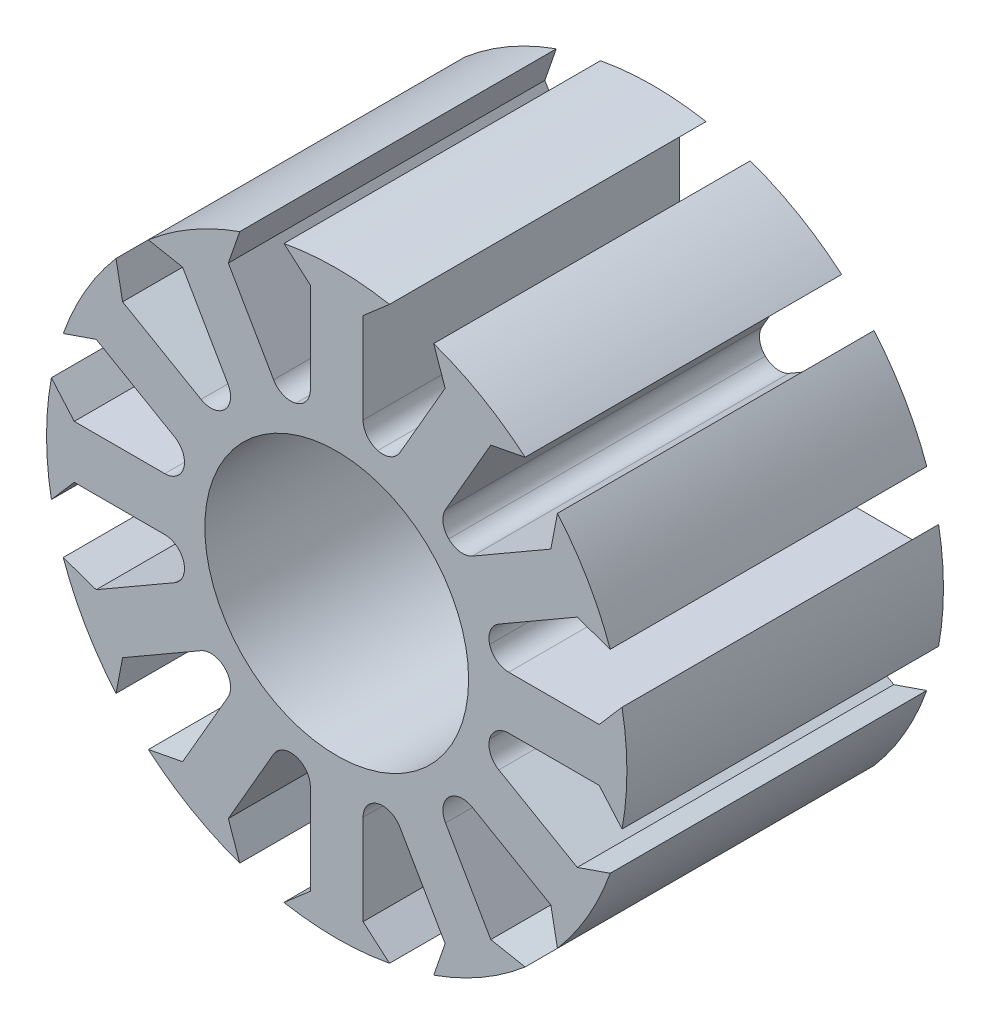
SolidWorks part; units mm, degrees
material "A286 Iron Base Superalloy"
ref_plane "Front Plane" through (0, 0, 0) normal (0, 0, 1) x (1, 0, 0)
ref_plane "Top Plane" through (0, 0, 0) normal (0, 1, 0) x (1, 0, 0)
ref_plane "Right Plane" through (0, 0, 0) normal (1, 0, 0) x (0, 0, -1)
sketch "Sketch1" plane through (0, 0, 0) normal (0, 0, 1) x (1, 0, 0)
  line L0 (-1, 9.9499) -> (-2, 10.8167)
  line L5 (1.5835, 4.7426) -> (4.1089, 9.1168)
  line L6 (3.3155, 3.7426) -> (5.841, 8.1168)
  line L11 (4.1089, 9.1168) -> (3.6763, 10.3675)
  line L12 (1, 4.899) -> (1, 9.9499)
  line L13 (1, 9.9499) -> (2, 10.8167)
  line L14 (5.841, 8.1168) -> (7.1404, 8.3675)
  line L16 (3.7426, 3.3155) -> (8.1168, 5.841)
  line L17 (-1, 4.899) -> (-1, 9.9499)
  line L18 (4.7426, 1.5835) -> (9.1168, 4.1089)
  line L19 (8.1168, 5.841) -> (8.3675, 7.1404)
  line L21 (9.1168, 4.1089) -> (10.3675, 3.6763)
  line L22 (4.899, 1) -> (9.9499, 1)
  line L23 (4.899, -1) -> (9.9499, -1)
  line L24 (9.9499, 1) -> (10.8167, 2)
  line L25 (9.9499, -1) -> (10.8167, -2)
  line L26 (4.7426, -1.5835) -> (9.1168, -4.1089)
  line L27 (3.7426, -3.3155) -> (8.1168, -5.841)
  line L28 (9.1168, -4.1089) -> (10.3675, -3.6763)
  line L29 (8.1168, -5.841) -> (8.3675, -7.1404)
  line L30 (3.3155, -3.7426) -> (5.841, -8.1168)
  line L31 (1.5835, -4.7426) -> (4.1089, -9.1168)
  line L32 (5.841, -8.1168) -> (7.1404, -8.3675)
  line L33 (4.1089, -9.1168) -> (3.6763, -10.3675)
  line L34 (1, -4.899) -> (1, -9.9499)
  line L35 (-1, -4.899) -> (-1, -9.9499)
  line L36 (1, -9.9499) -> (2, -10.8167)
  line L37 (-1, -9.9499) -> (-2, -10.8167)
  line L38 (-1.5835, -4.7426) -> (-4.1089, -9.1168)
  line L39 (-3.3155, -3.7426) -> (-5.841, -8.1168)
  line L40 (-4.1089, -9.1168) -> (-3.6763, -10.3675)
  line L41 (-5.841, -8.1168) -> (-7.1404, -8.3675)
  line L42 (-3.7426, -3.3155) -> (-8.1168, -5.841)
  line L43 (-4.7426, -1.5835) -> (-9.1168, -4.1089)
  line L44 (-8.1168, -5.841) -> (-8.3675, -7.1404)
  line L45 (-9.1168, -4.1089) -> (-10.3675, -3.6763)
  line L46 (-4.899, -1) -> (-9.9499, -1)
  line L47 (-4.899, 1) -> (-9.9499, 1)
  line L48 (-9.9499, -1) -> (-10.8167, -2)
  line L49 (-9.9499, 1) -> (-10.8167, 2)
  line L50 (-4.7426, 1.5835) -> (-9.1168, 4.1089)
  line L51 (-3.7426, 3.3155) -> (-8.1168, 5.841)
  line L52 (-9.1168, 4.1089) -> (-10.3675, 3.6763)
  line L53 (-8.1168, 5.841) -> (-8.3675, 7.1404)
  line L54 (-3.3155, 3.7426) -> (-5.841, 8.1168)
  line L55 (-1.5835, 4.7426) -> (-4.1089, 9.1168)
  line L56 (-5.841, 8.1168) -> (-7.1404, 8.3675)
  line L57 (-4.1089, 9.1168) -> (-3.6763, 10.3675)
  arc A0 (2, 10.8167) -> (-2, 10.8167) centre (0, 0) ccw
  arc A1 (-1, 4.899) -> (-1.5835, 4.7426) centre (0, 0) ccw
  arc A5 (-1, 4.899) -> (-1.5835, 4.7426) centre (0, 0) ccw
  arc A6 (7.1404, 8.3675) -> (3.6763, 10.3675) centre (0, 0) ccw
  arc A7 (3.7426, 3.3155) -> (3.3155, 3.7426) centre (0, 0) ccw
  arc A8 (10.3675, 3.6763) -> (8.3675, 7.1404) centre (0, 0) ccw
  arc A9 (4.899, 1) -> (4.7426, 1.5835) centre (0, 0) ccw
  arc A10 (10.8167, -2) -> (10.8167, 2) centre (0, 0) ccw
  arc A11 (4.7426, -1.5835) -> (4.899, -1) centre (0, 0) ccw
  arc A12 (8.3675, -7.1404) -> (10.3675, -3.6763) centre (0, 0) ccw
  arc A13 (3.3155, -3.7426) -> (3.7426, -3.3155) centre (0, 0) ccw
  arc A14 (3.6763, -10.3675) -> (7.1404, -8.3675) centre (0, 0) ccw
  arc A15 (1, -4.899) -> (1.5835, -4.7426) centre (0, 0) ccw
  arc A16 (-2, -10.8167) -> (2, -10.8167) centre (0, 0) ccw
  arc A17 (-1.5835, -4.7426) -> (-1, -4.899) centre (0, 0) ccw
  arc A18 (-7.1404, -8.3675) -> (-3.6763, -10.3675) centre (0, 0) ccw
  arc A19 (-3.7426, -3.3155) -> (-3.3155, -3.7426) centre (0, 0) ccw
  arc A20 (-10.3675, -3.6763) -> (-8.3675, -7.1404) centre (0, 0) ccw
  arc A21 (-4.899, -1) -> (-4.7426, -1.5835) centre (0, 0) ccw
  arc A22 (-10.8167, 2) -> (-10.8167, -2) centre (0, 0) ccw
  arc A23 (-4.7426, 1.5835) -> (-4.899, 1) centre (0, 0) ccw
  arc A24 (-8.3675, 7.1404) -> (-10.3675, 3.6763) centre (0, 0) ccw
  arc A25 (-3.3155, 3.7426) -> (-3.7426, 3.3155) centre (0, 0) ccw
  arc A26 (-3.6763, 10.3675) -> (-7.1404, 8.3675) centre (0, 0) ccw
  arc A27 (-1, 4.899) -> (-1.5835, 4.7426) centre (0, 0) ccw
  arc A28 (-1, 4.899) -> (-1.5835, 4.7426) centre (0, 0) ccw
  arc A29 (-1, 4.899) -> (-1.5835, 4.7426) centre (0, 0) ccw
  arc A30 (-1, 4.899) -> (-1.5835, 4.7426) centre (0, 0) ccw
  arc A31 (-1, 4.899) -> (-1.5835, 4.7426) centre (0, 0) ccw
  arc A32 (-1, 4.899) -> (-1.5835, 4.7426) centre (0, 0) ccw
  arc A33 (-1, 4.899) -> (-1.5835, 4.7426) centre (0, 0) ccw
  arc A34 (-1, 4.899) -> (-1.5835, 4.7426) centre (0, 0) ccw
  arc A35 (-1, 4.899) -> (-1.5835, 4.7426) centre (0, 0) ccw
  arc A36 (-1, 4.899) -> (-1.5835, 4.7426) centre (0, 0) ccw
  arc A37 (-3.3155, 3.7426) -> (-3.7426, 3.3155) centre (0, 0) ccw
  arc A38 (-3.3155, 3.7426) -> (-3.7426, 3.3155) centre (0, 0) ccw
  arc A39 (-3.3155, 3.7426) -> (-3.7426, 3.3155) centre (0, 0) ccw
  arc A40 (-3.3155, 3.7426) -> (-3.7426, 3.3155) centre (0, 0) ccw
  arc A41 (-3.3155, 3.7426) -> (-3.7426, 3.3155) centre (0, 0) ccw
  arc A42 (-3.3155, 3.7426) -> (-3.7426, 3.3155) centre (0, 0) ccw
  arc A43 (-3.3155, 3.7426) -> (-3.7426, 3.3155) centre (0, 0) ccw
  arc A44 (-3.3155, 3.7426) -> (-3.7426, 3.3155) centre (0, 0) ccw
  arc A45 (-3.3155, 3.7426) -> (-3.7426, 3.3155) centre (0, 0) ccw
  arc A46 (-3.3155, 3.7426) -> (-3.7426, 3.3155) centre (0, 0) ccw
  arc A47 (-3.3155, 3.7426) -> (-3.7426, 3.3155) centre (0, 0) ccw
  arc A48 (1.5835, 4.7426) -> (1, 4.899) centre (0, 0) ccw
  arc A49 (3.7426, 3.3155) -> (3.3155, 3.7426) centre (0, 0) ccw
  arc A50 (3.7426, 3.3155) -> (3.3155, 3.7426) centre (0, 0) ccw
  arc A51 (3.7426, 3.3155) -> (3.3155, 3.7426) centre (0, 0) ccw
  arc A52 (3.7426, 3.3155) -> (3.3155, 3.7426) centre (0, 0) ccw
  arc A53 (3.7426, 3.3155) -> (3.3155, 3.7426) centre (0, 0) ccw
  arc A54 (3.7426, 3.3155) -> (3.3155, 3.7426) centre (0, 0) ccw
  arc A55 (3.7426, 3.3155) -> (3.3155, 3.7426) centre (0, 0) ccw
  arc A56 (3.7426, 3.3155) -> (3.3155, 3.7426) centre (0, 0) ccw
  arc A57 (3.7426, 3.3155) -> (3.3155, 3.7426) centre (0, 0) ccw
  arc A58 (3.7426, 3.3155) -> (3.3155, 3.7426) centre (0, 0) ccw
  arc A59 (3.7426, 3.3155) -> (3.3155, 3.7426) centre (0, 0) ccw
  arc A60 (-4.7426, 1.5835) -> (-4.899, 1) centre (0, 0) ccw
  arc A61 (-4.7426, 1.5835) -> (-4.899, 1) centre (0, 0) ccw
  arc A62 (-4.7426, 1.5835) -> (-4.899, 1) centre (0, 0) ccw
  arc A63 (-4.7426, 1.5835) -> (-4.899, 1) centre (0, 0) ccw
  arc A64 (-4.7426, 1.5835) -> (-4.899, 1) centre (0, 0) ccw
  arc A65 (4.7426, -1.5835) -> (4.899, -1) centre (0, 0) ccw
  arc A66 (4.7426, -1.5835) -> (4.899, -1) centre (0, 0) ccw
  arc A67 (4.7426, -1.5835) -> (4.899, -1) centre (0, 0) ccw
  arc A68 (4.7426, -1.5835) -> (4.899, -1) centre (0, 0) ccw
  arc A69 (4.7426, -1.5835) -> (4.899, -1) centre (0, 0) ccw
  arc A70 (4.7426, -1.5835) -> (4.899, -1) centre (0, 0) ccw
  arc A71 (4.7426, -1.5835) -> (4.899, -1) centre (0, 0) ccw
  arc A72 (4.7426, -1.5835) -> (4.899, -1) centre (0, 0) ccw
  arc A73 (4.7426, -1.5835) -> (4.899, -1) centre (0, 0) ccw
  arc A74 (4.7426, -1.5835) -> (4.899, -1) centre (0, 0) ccw
  arc A75 (4.7426, -1.5835) -> (4.899, -1) centre (0, 0) ccw
  arc A76 (3.3155, -3.7426) -> (3.7426, -3.3155) centre (0, 0) ccw
  arc A77 (3.3155, -3.7426) -> (3.7426, -3.3155) centre (0, 0) ccw
  arc A78 (3.3155, -3.7426) -> (3.7426, -3.3155) centre (0, 0) ccw
  arc A79 (3.3155, -3.7426) -> (3.7426, -3.3155) centre (0, 0) ccw
  arc A80 (3.3155, -3.7426) -> (3.7426, -3.3155) centre (0, 0) ccw
  arc A81 (3.3155, -3.7426) -> (3.7426, -3.3155) centre (0, 0) ccw
  arc A82 (3.3155, -3.7426) -> (3.7426, -3.3155) centre (0, 0) ccw
  arc A83 (3.3155, -3.7426) -> (3.7426, -3.3155) centre (0, 0) ccw
  arc A84 (3.3155, -3.7426) -> (3.7426, -3.3155) centre (0, 0) ccw
  arc A85 (3.3155, -3.7426) -> (3.7426, -3.3155) centre (0, 0) ccw
  arc A86 (3.3155, -3.7426) -> (3.7426, -3.3155) centre (0, 0) ccw
  arc A87 (1, -4.899) -> (1.5835, -4.7426) centre (0, 0) ccw
  arc A88 (1, -4.899) -> (1.5835, -4.7426) centre (0, 0) ccw
  arc A89 (1, -4.899) -> (1.5835, -4.7426) centre (0, 0) ccw
  arc A90 (1, -4.899) -> (1.5835, -4.7426) centre (0, 0) ccw
  arc A91 (1, -4.899) -> (1.5835, -4.7426) centre (0, 0) ccw
  arc A92 (1, -4.899) -> (1.5835, -4.7426) centre (0, 0) ccw
  arc A93 (1, -4.899) -> (1.5835, -4.7426) centre (0, 0) ccw
  arc A94 (1, -4.899) -> (1.5835, -4.7426) centre (0, 0) ccw
  arc A95 (1, -4.899) -> (1.5835, -4.7426) centre (0, 0) ccw
  arc A96 (1, -4.899) -> (1.5835, -4.7426) centre (0, 0) ccw
  arc A97 (1, -4.899) -> (1.5835, -4.7426) centre (0, 0) ccw
  arc A98 (-1.5835, -4.7426) -> (-1, -4.899) centre (0, 0) ccw
  arc A99 (-1.5835, -4.7426) -> (-1, -4.899) centre (0, 0) ccw
  arc A100 (-1.5835, -4.7426) -> (-1, -4.899) centre (0, 0) ccw
  arc A101 (-1.5835, -4.7426) -> (-1, -4.899) centre (0, 0) ccw
  arc A102 (-1.5835, -4.7426) -> (-1, -4.899) centre (0, 0) ccw
  arc A103 (-1.5835, -4.7426) -> (-1, -4.899) centre (0, 0) ccw
  arc A104 (-1.5835, -4.7426) -> (-1, -4.899) centre (0, 0) ccw
  arc A105 (-1.5835, -4.7426) -> (-1, -4.899) centre (0, 0) ccw
  arc A106 (-1.5835, -4.7426) -> (-1, -4.899) centre (0, 0) ccw
  arc A107 (-1.5835, -4.7426) -> (-1, -4.899) centre (0, 0) ccw
  arc A108 (-1.5835, -4.7426) -> (-1, -4.899) centre (0, 0) ccw
  arc A109 (-4.7426, 1.5835) -> (-4.899, 1) centre (0, 0) ccw
  arc A110 (-4.7426, 1.5835) -> (-4.899, 1) centre (0, 0) ccw
  arc A111 (-4.7426, 1.5835) -> (-4.899, 1) centre (0, 0) ccw
  arc A112 (-4.7426, 1.5835) -> (-4.899, 1) centre (0, 0) ccw
  arc A113 (-4.7426, 1.5835) -> (-4.899, 1) centre (0, 0) ccw
  arc A114 (-4.7426, 1.5835) -> (-4.899, 1) centre (0, 0) ccw
  arc A115 (-4.899, -1) -> (-4.7426, -1.5835) centre (0, 0) ccw
  arc A116 (-4.899, -1) -> (-4.7426, -1.5835) centre (0, 0) ccw
  arc A117 (-4.899, -1) -> (-4.7426, -1.5835) centre (0, 0) ccw
  arc A118 (-4.899, -1) -> (-4.7426, -1.5835) centre (0, 0) ccw
  arc A119 (-4.899, -1) -> (-4.7426, -1.5835) centre (0, 0) ccw
  arc A120 (-4.899, -1) -> (-4.7426, -1.5835) centre (0, 0) ccw
  arc A121 (-4.899, -1) -> (-4.7426, -1.5835) centre (0, 0) ccw
  arc A122 (-4.899, -1) -> (-4.7426, -1.5835) centre (0, 0) ccw
  arc A123 (-4.899, -1) -> (-4.7426, -1.5835) centre (0, 0) ccw
  arc A124 (-4.899, -1) -> (-4.7426, -1.5835) centre (0, 0) ccw
  arc A125 (-4.899, -1) -> (-4.7426, -1.5835) centre (0, 0) ccw
  arc A126 (-3.7426, -3.3155) -> (-3.3155, -3.7426) centre (0, 0) ccw
  arc A127 (-3.7426, -3.3155) -> (-3.3155, -3.7426) centre (0, 0) ccw
  arc A128 (-3.7426, -3.3155) -> (-3.3155, -3.7426) centre (0, 0) ccw
  arc A129 (-3.7426, -3.3155) -> (-3.3155, -3.7426) centre (0, 0) ccw
  arc A130 (-3.7426, -3.3155) -> (-3.3155, -3.7426) centre (0, 0) ccw
  arc A131 (-3.7426, -3.3155) -> (-3.3155, -3.7426) centre (0, 0) ccw
  arc A132 (-3.7426, -3.3155) -> (-3.3155, -3.7426) centre (0, 0) ccw
  arc A133 (-3.7426, -3.3155) -> (-3.3155, -3.7426) centre (0, 0) ccw
  arc A134 (-3.7426, -3.3155) -> (-3.3155, -3.7426) centre (0, 0) ccw
  arc A135 (-3.7426, -3.3155) -> (-3.3155, -3.7426) centre (0, 0) ccw
  arc A136 (-3.7426, -3.3155) -> (-3.3155, -3.7426) centre (0, 0) ccw
  arc A137 (4.899, 1) -> (4.7426, 1.5835) centre (0, 0) ccw
  arc A138 (4.899, 1) -> (4.7426, 1.5835) centre (0, 0) ccw
  arc A139 (4.899, 1) -> (4.7426, 1.5835) centre (0, 0) ccw
  arc A140 (4.899, 1) -> (4.7426, 1.5835) centre (0, 0) ccw
  arc A141 (4.899, 1) -> (4.7426, 1.5835) centre (0, 0) ccw
  arc A142 (4.899, 1) -> (4.7426, 1.5835) centre (0, 0) ccw
  arc A143 (4.899, 1) -> (4.7426, 1.5835) centre (0, 0) ccw
  arc A144 (4.899, 1) -> (4.7426, 1.5835) centre (0, 0) ccw
  arc A145 (4.899, 1) -> (4.7426, 1.5835) centre (0, 0) ccw
  arc A146 (4.899, 1) -> (4.7426, 1.5835) centre (0, 0) ccw
  arc A147 (4.899, 1) -> (4.7426, 1.5835) centre (0, 0) ccw
  point P77 (0, 0)
  dimension "D1" = 12
extrude "Boss-Extrude1" add sketch "Sketch1" along normal blind 12 contours L5 A48 L12 L13 A0 L0 L17 A1 L55 L57 A26 L56 L54 A25 L51 L53 A24 L52 L50 A23 L47 L49 A22 L48 L46 A21 L43 L45 A20 L44 L42 A19 L39 L41 A18 L40 L38 A17 L35 L37 A16 L36 L34 A15 L31 L33 A14 L32 L30 A13 L27 region at (0, 0, 0)
sketch "Sketch2" plane through (0, 0, 12) normal (0, 0, 1) x (1, 0, 0)
  circle A0 centre (0, 0) radius 6
extrude "Boss-Extrude2" add sketch "Sketch2" against normal blind 12
sketch "Sketch3" plane through (0, 0, 12) normal (0, 0, 1) x (1, 0, 0)
  circle A0 centre (0, 0) radius 5
extrude "Cut-Extrude1" cut sketch "Sketch3" against normal blind 12
fillet "Fillet1" radius 0.75 1 edges at (-4.6235, 3.8241, 6)
fillet "Fillet2" radius 0.75 1 edges at (-3.8241, 4.6235, 6)
fillet "Fillet3" radius 0.75 11 edges at (-5.9161, 1, 6) (-5.6235, -2.092, 6) (-3.8241, -4.6235, 6) (-1, -5.9161, 6) (2.092, -5.6235, 6) (4.6235, -3.8241, 6) (5.9161, -1, 6) (5.6235, 2.092, 6) (3.8241, 4.6235, 6) (1, 5.9161, 6) (-2.092, 5.6235, 6)
fillet "Fillet4" radius 0.75 11 edges at (-5.9161, -1, 6) (-4.6235, -3.8241, 6) (-2.092, -5.6235, 6) (1, -5.9161, 6) (3.8241, -4.6235, 6) (5.6235, -2.092, 6) (5.9161, 1, 6) (4.6235, 3.8241, 6) (2.092, 5.6235, 6) (-1, 5.9161, 6) (-5.6235, 2.092, 6)
